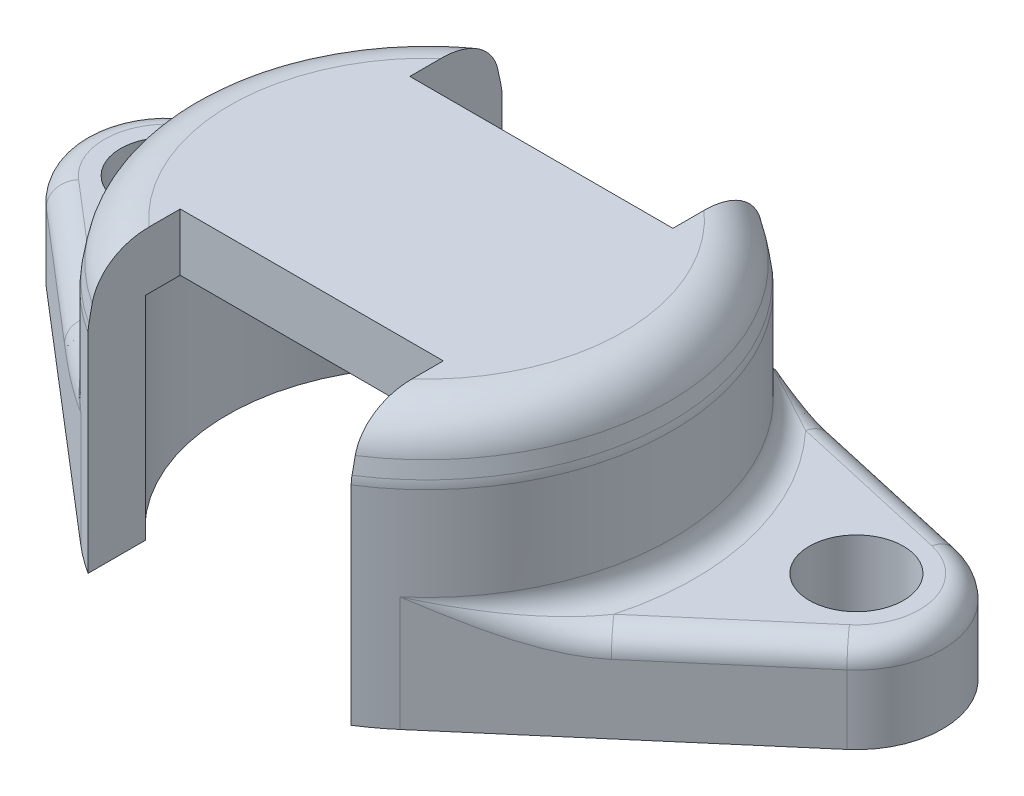
SolidWorks part; units mm, degrees
ref_plane "Front Plane" through (0, 0, 0) normal (0, 0, 1) x (1, 0, 0)
ref_plane "Top Plane" through (0, 0, 0) normal (0, 1, 0) x (1, 0, 0)
ref_plane "Right Plane" through (0, 0, 0) normal (1, 0, 0) x (0, 0, -1)
sketch "Sketch1" plane through (0, 0, 0) normal (0, 1, 0) x (1, 0, 0)
  circle A0 centre (-19.05, 0) radius 2.6035 construction
  circle A1 centre (0, 0) radius 11.0236 construction
  circle A2 centre (19.05, 0) radius 2.6035 construction
  dimension "D1" = 22.0472
  dimension "D2" = 5.207
  dimension "D4" = 38.1
  dimension "D3" = 19.05
sketch "Sketch2" plane through (0, 0, 0) normal (0, 1, 0) x (1, 0, 0)
  circle A0 centre (0, 0) radius 11.0236
  circle A1 centre (0, 0) radius 13.5636
  dimension "D1" = 22.0472
  dimension "D2" = 2.54
extrude "Boss-Extrude1" add sketch "Sketch2" along normal blind 11.7348
sketch "Sketch3" plane through (0, 11.7348, 0) normal (0, 1, 0) x (1, 0, 0)
  circle A0 centre (0, 0) radius 13.5636
extrude "Boss-Extrude2" add sketch "Sketch3" along normal blind 3.175 draft 10
sketch "Sketch4" plane through (0, 0, 0) normal (0, -1, 0) x (1, 0, 0)
  line L0 (-22.1478, -1.1097) -> (-8.8227, 10.302)
  line L1 (-20.0975, -9.3728) -> (-2.9832, -13.2315)
  line L2 (0, 13.5636) -> (0, -13.5636) construction
  line L3 (20.0975, -9.3728) -> (2.9832, -13.2315)
  line L4 (22.1478, -1.1097) -> (8.8227, 10.302)
  circle A0 centre (-19.05, -4.7269) radius 2.6035
  arc A3 (-22.1478, -1.1097) -> (-20.0975, -9.3728) centre (-19.05, -4.7269) ccw
  circle A5 centre (0, 0) radius 13.5636 construction
  arc A9 (-2.9832, -13.2315) -> (-8.8227, 10.302) centre (0, 0) cw
  arc A11 (2.9832, -13.2315) -> (8.8227, 10.302) centre (0, 0) ccw
  arc A12 (22.1478, -1.1097) -> (20.0975, -9.3728) centre (19.05, -4.7269) cw
  circle A13 centre (19.05, -4.7269) radius 2.6035
  dimension "D1" = 9.525
  dimension "D2" = 4.7269
  dimension "D4" = 5.207
  dimension "D3" = 19.05
extrude "Boss-Extrude4" add sketch "Sketch4" against normal blind 5.08
fillet "Fillet1" radius 1.27 2 edges at (13.1644, 5.08, -3.2665) (-13.1644, 5.08, -3.2665)
fillet "Fillet2" radius 2.54 2 edges at (0, 11.7348, 13.5636) (0, 14.9098, 13.0038)
fillet "Fillet3" radius 1.27 10 edges at (6.3637, 5.3925, -12.4693) (14.4695, 5.08, -10.6417) (23.6723, 5.08, -5.8739) (11.4547, 5.3925, 8.0479) (-6.3637, 5.3925, -12.4693) (-14.4695, 5.08, -10.6417) (-23.6723, 5.08, -5.8739) (-11.4547, 5.3925, 8.0479) (17.7659, 5.08, 2.643) (-17.7659, 5.08, 2.643)
sketch "Sketch5" plane through (0, 0, 0) normal (0, -1, 0) x (1, 0, 0)
  line L0 (-11.0236, 0) -> (11.0236, 0) construction
  line L1 (-7.2771, -6.35) -> (7.2771, -6.35)
  line L2 (-7.2771, -6.35) -> (-7.2771, -18.3266)
  line L3 (-7.2771, -18.3266) -> (7.2771, -18.3266)
  line L4 (7.2771, -6.35) -> (7.2771, -18.3266)
  line L5 (7.2771, 6.35) -> (7.2771, 18.3266)
  line L6 (-7.2771, 18.3266) -> (7.2771, 18.3266)
  line L7 (-7.2771, 6.35) -> (-7.2771, 18.3266)
  line L8 (-7.2771, 6.35) -> (7.2771, 6.35)
  circle A0 centre (0, 0) radius 11.0236 construction
  circle A1 centre (0, 0) radius 11.0236 construction
  point P4 (0, -6.35)
  dimension "D1" = 14.5542
  dimension "D2" = 6.35
extrude "Cut-Extrude1" cut sketch "Sketch5" against normal through all
